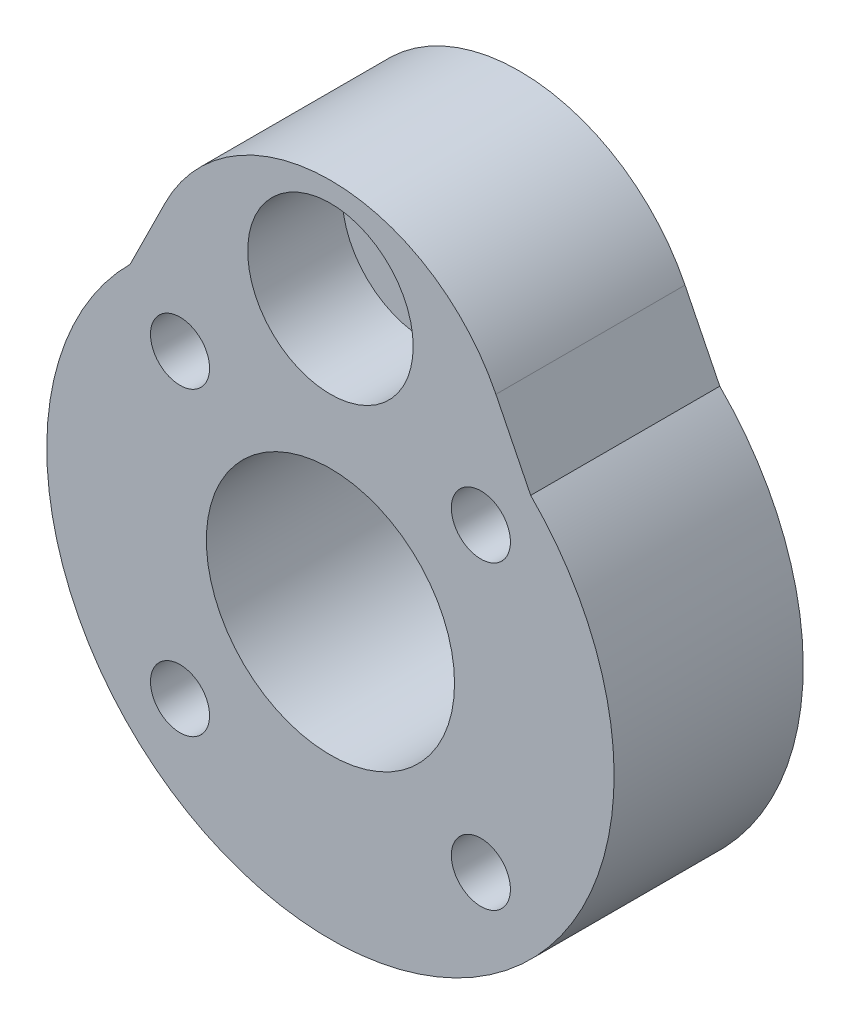
SolidWorks part; units mm, degrees
ref_plane "Front" through (0, 0, 0) normal (0, 0, 1) x (1, 0, 0)
ref_plane "Top" through (0, 0, 0) normal (0, 1, 0) x (1, 0, 0)
ref_plane "Right" through (0, 0, 0) normal (1, 0, 0) x (0, 0, -1)
sketch "Esquisse1" plane through (0, 0, 0) normal (0, 0, 1) x (1, 0, 0)
  circle A0 centre (0, 0) radius 12
  circle A1 centre (0, 0) radius 5.25
  dimension "D1" = 24
  dimension "D2" = 10.5
extrude "Boss.-Extru.1" add sketch "Esquisse1" along normal blind 8
sketch "Esquisse2" plane through (0, 0, 8) normal (0, 0, 1) x (1, 0, 0)
  line L0 (0, 0) -> (0, 8) construction
  line L1 (7, 11.4681) -> (-7, 11.4681) construction
  line L2 (0, 8) -> (0, 23.3526) construction
  line L3 (-7, 11.4681) -> (-8.4705, 8.5)
  line L4 (-8.4705, 8.5) -> (0, 8.5)
  line L5 (8.4705, 8.5) -> (0, 8.5)
  line L6 (7, 11.4681) -> (8.4705, 8.5)
  arc A0 (-7, 11.4681) -> (7, 11.4681) centre (0, 8) cw
  circle A1 centre (0, 0) radius 12 construction
  dimension "D1" = 8
  dimension "D2" = 14
  dimension "D3" = 8.5
extrude "Boss.-Extru.2" add sketch "Esquisse2" against normal up to surface (8 mm away) up to face at (12, 0, 0)
sketch "Esquisse3" plane through (0, 0, 8) normal (0, 0, 1) x (1, 0, 0)
  line L0 (0, 0) -> (-6.364, 6.364) construction
  line L1 (0, 0) -> (-4.1556, 0) construction
  circle A0 centre (-6.364, 6.364) radius 1.25
  circle A1 centre (6.364, 6.364) radius 1.25
  circle A2 centre (6.364, -6.364) radius 1.25
  circle A3 centre (-6.364, -6.364) radius 1.25
  point P13 (0, 0)
  dimension "D1" = 9
  dimension "D2" = 2.5
  dimension "D4" = 45
  dimension "D3" = 4
extrude "Enlèv. mat.-Extru.1" cut sketch "Esquisse3" against normal through all
sketch "Esquisse4" plane through (0, 0, 8) normal (0, 0, 1) x (1, 0, 0)
  line L0 (-7, 11.4681) -> (7, 11.4681) construction
  circle A0 centre (0, 11.4681) radius 2
  dimension "D1" = 4
extrude "Enlèv. mat.-Extru.2" cut sketch "Esquisse4" against normal through all
sketch "Esquisse5" plane through (0, 0, 8) normal (0, 0, 1) x (1, 0, 0)
  circle A0 centre (0, 11.4681) radius 3.5
  dimension "D1" = 7
extrude "Enlèv. mat.-Extru.3" cut sketch "Esquisse5" against normal blind 4
